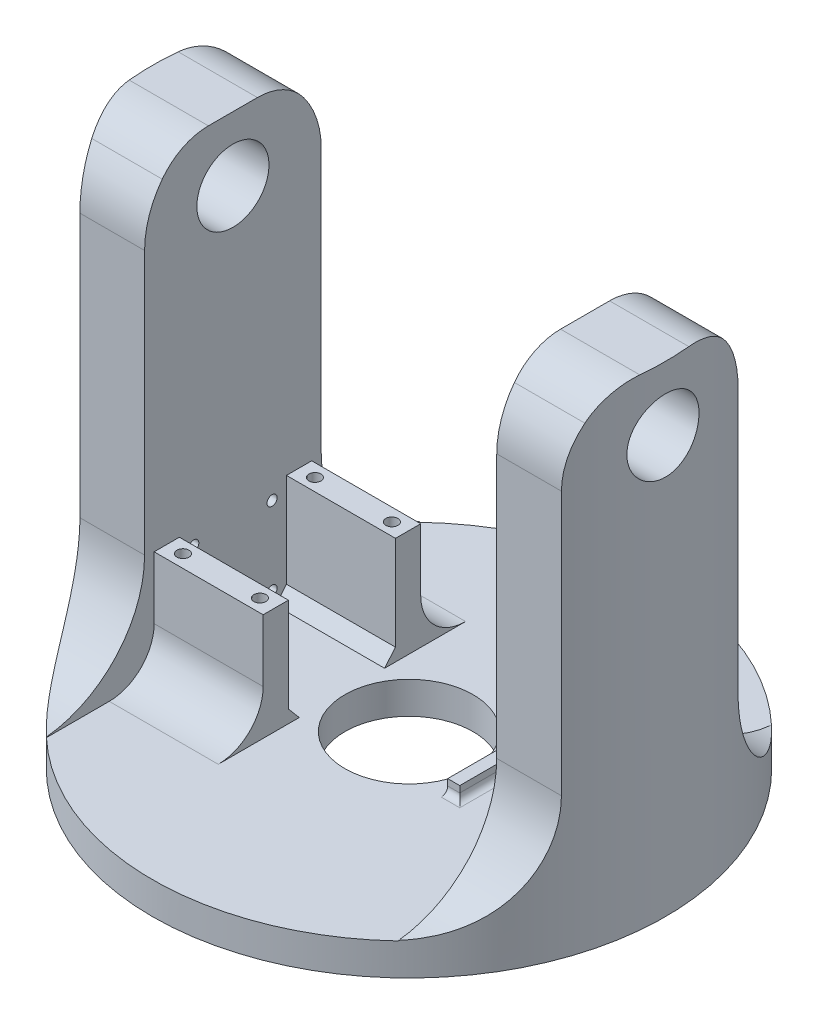
SolidWorks part; units mm, degrees
ref_plane "Front Plane" through (0, 0, 0) normal (0, 0, 1) x (1, 0, 0)
ref_plane "Top Plane" through (0, 0, 0) normal (0, 1, 0) x (1, 0, 0)
ref_plane "Right Plane" through (0, 0, 0) normal (1, 0, 0) x (0, 0, -1)
sketch "Sketch1" plane through (0, 0, 0) normal (0, 1, 0) x (1, 0, 0)
  circle A0 centre (0, 0) radius 101.6
  dimension "D1" = 203.2
extrude "Boss-Extrude1" add sketch "Sketch1" along normal blind 12.7
sketch "Sketch2" plane through (0, 12.7, 0) normal (0, 1, 0) x (1, 0, 0)
  line L0 (0, -148.3769) -> (0, 148.3769) construction
  line L1 (-191.7926, 0) -> (191.7926, 0) construction
  line L2 (69.7492, 34.9877) -> (95.3856, -34.9877) construction
  line L3 (-69.7492, -34.9877) -> (-95.3856, -34.9877)
  line L4 (-69.7492, -34.9877) -> (-69.7492, 34.9877)
  line L5 (-69.7492, 34.9877) -> (-95.3856, 34.9877)
  line L7 (-69.7492, -34.9877) -> (-95.3856, 34.9877) construction
  line L8 (-69.7492, 34.9877) -> (-95.3856, -34.9877) construction
  line L9 (69.7492, -34.9877) -> (95.3856, 34.9877) construction
  line L11 (69.7492, 34.9877) -> (95.3856, 34.9877)
  line L12 (69.7492, -34.9877) -> (95.3856, -34.9877)
  line L13 (69.7492, -34.9877) -> (69.7492, 34.9877)
  circle A0 centre (0, 0) radius 101.6 construction
  arc A1 (-95.3856, 34.9877) -> (-95.3856, -34.9877) centre (0, 0) ccw
  arc A2 (95.3856, -34.9877) -> (95.3856, 34.9877) centre (0, 0) ccw
  point P0 (-82.5674, 0)
  point P4 (0, 0)
  point P8 (0, 0)
  point P19 (82.5674, 0)
extrude "Boss-Extrude3" add sketch "Sketch2" along normal blind 177.8
fillet "Fillet3" radius 43.18 4 edges at (82.5674, 12.7, 34.9877) (82.5674, 12.7, -34.9877) (-82.5674, 12.7, -34.9877) (-82.5674, 12.7, 34.9877)
sketch "Sketch3" plane through (0, 12.7, 0) normal (0, 1, 0) x (1, 0, 0)
  circle A0 centre (0, 0) radius 25.4
  dimension "D1" = 50.8
extrude "Cut-Extrude1" cut sketch "Sketch3" against normal through all
sketch "Sketch4" plane through (69.7492, 0, 0) normal (-1, 0, 0) x (0, 0, 1)
  line L0 (34.9877, 190.5) -> (-34.9877, 190.5) construction
  circle A0 centre (0, 165.1) radius 14.2875
  dimension "D1" = 28.575
  dimension "D2" = 25.4
extrude "Cut-Extrude2" cut sketch "Sketch4" against normal through all and the other way through all
sketch "Sketch5" plane through (69.7492, 0, 0) normal (-1, 0, 0) x (0, 0, 1)
  line L1 (-34.9877, 190.5) -> (-34.9877, 55.88) construction
  line L4 (34.9877, 160.3668) -> (34.9877, 209.9928)
  line L5 (34.9877, 209.9928) -> (-34.9877, 209.9928)
  line L6 (-34.9877, 160.3668) -> (-34.9877, 209.9928)
  line L7 (-20.1605, 188.9622) -> (-34.9877, 209.9928) construction
  line L8 (34.9877, 209.9928) -> (20.1605, 188.9622) construction
  arc A0 (34.9877, 160.3668) -> (-34.9877, 160.3668) centre (0, 160.3668) ccw
extrude "Cut-Extrude3" cut sketch "Sketch5" against normal through all and the other way through all
fillet "Fillet4" radius 22.86 4 edges at (-84.8907, 190.5, 17.7801) (-84.8907, 190.5, -17.7801) (84.8907, 190.5, 17.7801) (84.8907, 190.5, -17.7801)
sketch "Sketch7" plane through (0, 12.7, 0) normal (0, 1, 0) x (1, 0, 0)
  line L0 (-69.7492, -73.8756) -> (-69.7492, 73.8756) construction
  line L1 (-69.7492, 31.209) -> (-26.5692, 31.209)
  line L2 (-69.7492, 31.209) -> (-69.7492, 21.209)
  line L3 (-69.7492, 21.209) -> (-26.5692, 21.209)
  line L4 (-26.5692, 31.209) -> (-26.5692, 21.209)
  line L5 (-48.1592, -21.209) -> (-48.1592, 21.209) construction
  line L6 (-69.7492, -21.209) -> (-26.5692, -21.209)
  line L7 (-69.7492, -21.209) -> (-69.7492, -31.209)
  line L8 (-69.7492, -31.209) -> (-26.5692, -31.209)
  line L9 (-26.5692, -21.209) -> (-26.5692, -31.209)
  line L10 (-48.1592, 0) -> (-69.7492, 0) construction
  dimension "D1" = 10
  dimension "D2" = 10
  dimension "D3" = 42.418
  dimension "D4" = 43.18
  dimension "D5" = 43.18
  dimension "D6" = 21.209
extrude "Boss-Extrude4" add sketch "Sketch7" along normal blind 42.418
sketch "Sketch8" plane through (-69.7492, 0, 0) normal (1, 0, 0) x (0, 0, -1)
  line L0 (-21.209, 17.78) -> (-21.209, 12.7)
  line L1 (-21.209, 55.118) -> (-21.209, 12.7) construction
  line L2 (-21.209, 12.7) -> (-16.891, 12.7)
  line L3 (-21.209, 12.7) -> (21.209, 12.7) construction
  line L4 (-16.891, 12.7) -> (-21.209, 17.78)
  line L5 (0, 12.7) -> (0, 49.0162) construction
  line L6 (16.891, 12.7) -> (21.209, 17.78)
  line L7 (21.209, 12.7) -> (16.891, 12.7)
  line L8 (21.209, 17.78) -> (21.209, 12.7)
  dimension "D1" = 5.08
  dimension "D2" = 4.318
extrude "Boss-Extrude5" add sketch "Sketch8" along normal up to surface (43.18 mm away) up to face at (-26.5692, 33.909, -26.209)
fillet "Fillet5" radius 17.78 2 edges at (-48.1592, 12.7, 31.209) (-48.1592, 12.7, -31.209)
sketch "Sketch9" plane through (0, 55.118, 0) normal (0, 1, 0) x (1, 0, 0)
  line L0 (-69.7492, -21.209) -> (-69.7492, -31.209) construction
  line L1 (-69.7492, -31.209) -> (-26.5692, -31.209) construction
  line L2 (-69.7492, 0) -> (-40.8124, 0) construction
  line L3 (-69.7492, -16.891) -> (-69.7492, 16.891) construction
  circle A0 centre (-32.9192, -26.129) radius 2.4003
  circle A1 centre (-63.3992, -26.129) radius 2.4003
  circle A2 centre (-32.9192, 26.129) radius 2.4003
  circle A3 centre (-63.3992, 26.129) radius 2.4003
  dimension "D1" = 4.8006
  dimension "D2" = 4.8006
  dimension "D3" = 30.48
  dimension "D5" = 5.08
  dimension "D4" = 6.35
extrude "Cut-Extrude4" cut sketch "Sketch9" against normal blind 7.62
sketch "Sketch10" plane through (-69.7492, 0, 0) normal (1, 0, 0) x (0, 0, -1)
  line L0 (25.4, 12.7) -> (-25.4, 12.7) construction
  line L1 (0, 12.7) -> (0, 58.6858) construction
  circle A0 centre (-15.5, 49.35) radius 2
  circle A1 centre (-15.5, 18.35) radius 2
  circle A2 centre (15.5, 18.35) radius 2
  circle A3 centre (15.5, 49.35) radius 2
  point P13 (-15.3599, 49.35)
  dimension "D1" = 4
  dimension "D2" = 4
  dimension "D3" = 5.65
  dimension "D4" = 31
  dimension "D5" = 31
extrude "Cut-Extrude5" cut sketch "Sketch10" against normal blind 7.62
sketch "Sketch11" plane through (0, 12.7, 0) normal (0, 1, 0) x (1, 0, 0)
  line L1 (28.8552, -13.5335) -> (33.6421, -13.5335)
  line L2 (28.8552, -13.5335) -> (28.8552, 13.5335)
  line L3 (28.8552, 13.5335) -> (33.6421, 13.5335)
  line L4 (33.6421, -13.5335) -> (33.6421, 13.5335)
  line L5 (28.8552, -13.5335) -> (33.6421, 13.5335) construction
  line L6 (28.8552, 13.5335) -> (33.6421, -13.5335) construction
  line L7 (69.7492, 73.8756) -> (69.7492, -73.8756) construction
  point P0 (31.2487, 0)
  dimension "D1" = 40.894
extrude "Boss-Extrude6" add sketch "Sketch11" along normal blind 5.08
fillet "Fillet7" radius 2.54 3 edges at (31.2487, 12.7, 13.5335) (31.2487, 12.7, -13.5335) (33.6421, 12.7, 0)
